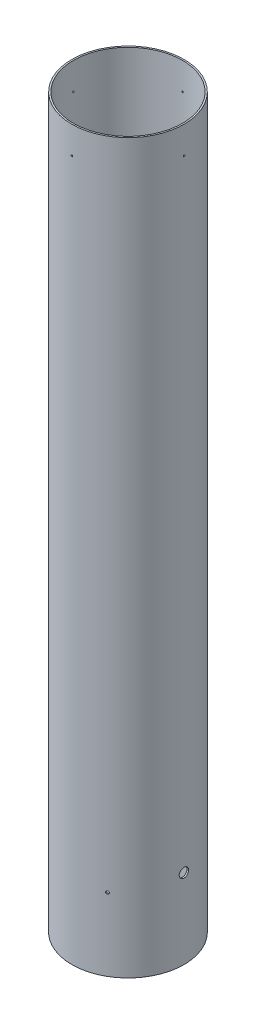
SolidWorks part; units mm, degrees
material "A-Glass Fiber"
ref_plane "Front Plane" through (0, 0, 0) normal (0, 0, 1) x (1, 0, 0)
ref_plane "Top Plane" through (0, 0, 0) normal (0, 1, 0) x (1, 0, 0)
ref_plane "Right Plane" through (0, 0, 0) normal (1, 0, 0) x (0, 0, -1)
sketch "Sketch1" plane through (0, 0, 0) normal (0, 1, 0) x (1, 0, 0)
  circle A0 centre (0, 0) radius 76.1746
  circle A1 centre (0, 0) radius 78.359
  dimension "D1" = 156.718
  dimension "D2" = 152.3492
extrude "Boss-Extrude1" add sketch "Sketch1" along normal blind 1016
ref_axis "Axis1" through (0, 1016, 0) along (0, -1, 0)
sketch "Sketch2" plane through (0, 0, 0) normal (1, 0, 0) x (0, 0, -1)
  line L0 (78.359, 1016) -> (-78.359, 1016) construction
  circle A0 centre (0, 977.9) radius 1.0922
  dimension "D1" = 2.1844
  dimension "D2" = 38.1
extrude "Cut-Extrude1" cut sketch "Sketch2" against normal through all
pattern_circular "CirPattern1" count 4 over 360 about axis through (0, 1016, 0) along (0, 1, 0) of "Cut-Extrude1"
hole_wizard "1/2 Clearance Hole1" positions "Sketch3" profile "Sketch4" hole size "1/2" standard "ANSI Inch"
sketch "Sketch3" plane through (0, 0, 0) normal (1, 0, 0) x (0, 0, -1)
  point P0 (0, 111.125)
  dimension "D1" = 111.125
sketch "Sketch4" plane through (0, 111.125, 0) normal (0, 1, 0) x (0, 0, 1)
  line L0 (0, 0) -> (0, 92.8345)
  line L1 (0, 92.8345) -> (6.5481, 88.9)
  line L2 (6.5481, 88.9) -> (6.5481, 0)
  line L5 (6.5481, 0) -> (0, 0)
  line L10 (0, 92.8345) -> (-6.5481, 88.9) construction
  line L11 (0, -6.35) -> (0, 107.95) construction
  dimension "Hole Dia." = 13.0962
  dimension "Hole Depth" = 88.9
  dimension "Drill Angle" = 118
hole_wizard "Ø4.0 (4) Diameter Hole1" positions "Sketch5" profile "Sketch6" hole size "Ø4.0" standard "ANSI Metric"
sketch "Sketch5" plane through (0, 0, 0) normal (1, 0, 0) x (0, 0, -1)
  point P0 (0, 101.6)
  dimension "D1" = 101.6
sketch "Sketch6" plane through (0, 101.6, 0) normal (0, 1, 0) x (0, 0, -1)
  line L0 (0, 0) -> (0, 90.1017)
  line L1 (0, 90.1017) -> (2, 88.9)
  line L2 (2, 88.9) -> (2, 0)
  line L5 (2, 0) -> (0, 0)
  line L10 (0, 90.1017) -> (-2, 88.9) construction
  line L11 (0, -6.35) -> (0, 107.95) construction
  dimension "Hole Dia." = 4
  dimension "Hole Depth" = 88.9
  dimension "Drill Angle" = 118
pattern_circular "CirPattern2" count 3 over 360 about axis through (0, 0, 0) along (0, 1, 0) of "Ø4.0 (4) Diameter Hole1"
equation "\"Fwd_Tube_Length\" = 40in"
equation "\"D1@Boss-Extrude1\" = \"Fwd_Tube_Length\""
equation "\"BKHD_Screw_Diam\"= 3.5mm"
equation "\"Fwd_BKHD_From_Top\" = 18in"
equation "\"Bodytube_OD\" = 6.17in"
equation "\"Bodytube_ID\" = 5.998in"
equation "\"D2@Sketch1\"=\"Bodytube_ID\""
equation "\"D1@Sketch1\"=\"Bodytube_OD\""
equation "\"Shear_Screw_Diameter\" = 0.086in"
equation "\"Shear_Screw_Coupler_Location\" = 4.5in"
equation "\"Motor_OD\" = 4in"
equation "\"Mid_Tube_Length\"= 1in"
equation "\"Mid_Coupler_Length\" = 13in"
equation "\"Aft_Section_Length\"= 39in"
equation "\"AB_Coupler_OD_Length\"= 1in"
equation "\"AB_Coupling_Section_Length\"= 0.375in"
equation "\"AB_Coupler_Length\"= \"AB_Coupler_OD_Length\" + \"AB_Coupling_Section_Length\" * 2"
equation "\"Cutout_Angle\" = 80"
equation "\"AB_Paddle_Height\" = 0.375in"
equation "\"AB_Coupler_Num_Screws\"= 4"
equation "\"AB_BKHD_Thickness\" = 0.375in"
equation "\"AB_Mount_From_Bottom\" = 23.175in"
equation "\"Num_Cutouts\" = 3"
equation "\"AB_Coupler_OD\"= 6.17in"
equation "\"AB_Coupler_ID\"= 5.75in"
equation "\"AB_Coupler_Surface_Diameter\"= 5.998in"
equation "\"AB_Coupling_Screw_Diameter\"= 0.15748in"
equation "\"AB_Central_Bushing_Length\" = .4724in"
equation "\"Lead_Screw_Dist\" = 3.4in"
equation "\"Lead_Screw_Diam\" = 0.386in"
equation "\"Lead_Screw_Length\" = (\"Mid_Coupler_Length\" + 2*0.375in + 2*0.5in)"
equation "\"Paddle_Pin_Offset\" = .25in"
equation "\"Paddle_Pin_Radius\" = 2.25in"
equation "\"SS_Paddle_Pin_Radius\" = 2.25*0.66in"
equation "\"Paddle_Gear_OD\" = 3.2in"
equation "\"Drive_Gear_OD\" = 1.7in"
equation "\"Fin_Thickness\"= .118in"
equation "\"Guiderail_Cutout_Diameter\"= 1.5in"
equation "\"DB9_Hole_Dist\" = 25mm"
equation "\"DB9_Relief_Width\" = 0.47in"
equation "\"DB9_Relief_Hole_Offset\" = 0.09in"
equation "\"Airbrakes_Wire_Hole_Dia\" = .25in"
equation "\"Airbrakes_Wire_Hole_Dist\" = 1.1in"
equation "\"Servo_Gear_Offset\" = 0.5in"
equation "\"D1@Sketch2\"=\"Shear_Screw_Diameter\""
equation "\"FWD_Shear_Screw_Dist\" = 1.5in"
equation "\"D2@Sketch2\"=\"FWD_Shear_Screw_Dist\""
